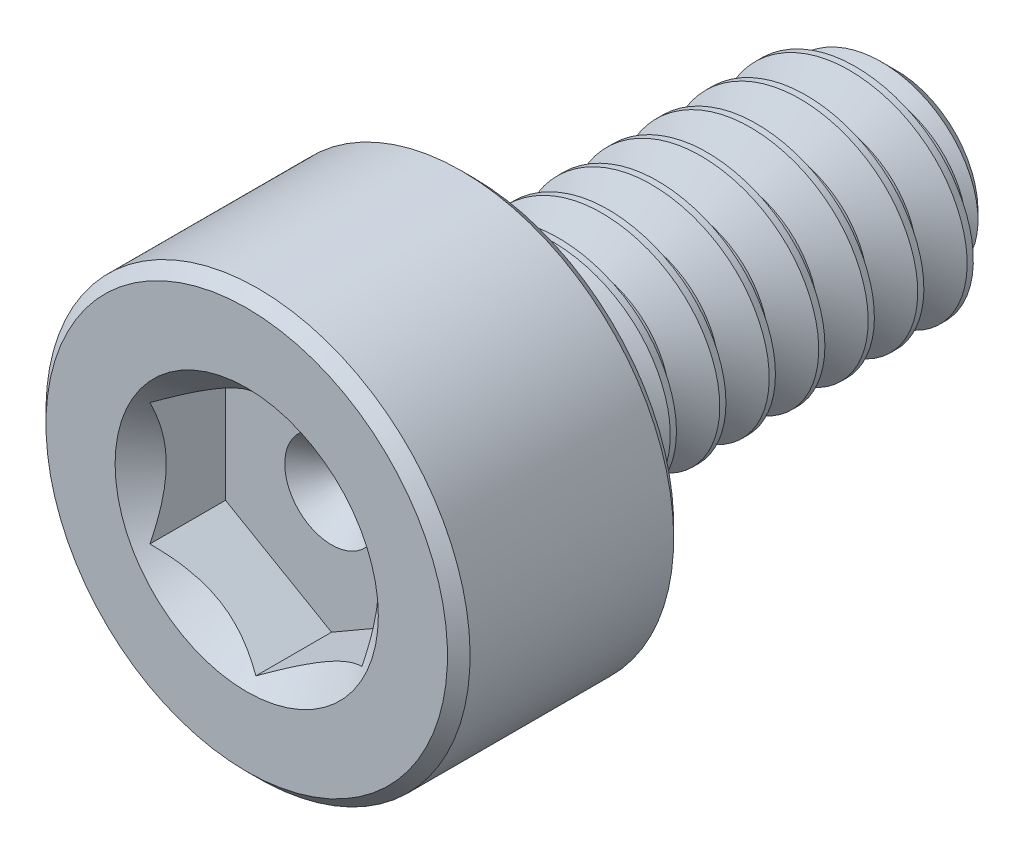
SolidWorks part; units mm, degrees
ref_plane "Front Plane" through (0, 0, 0) normal (0, 0, 1) x (1, 0, 0)
ref_plane "Top Plane" through (0, 0, 0) normal (0, 1, 0) x (1, 0, 0)
ref_plane "Right Plane" through (0, 0, 0) normal (1, 0, 0) x (0, 0, -1)
sketch "Sketch1" plane through (0, 0, 0) normal (1, 0, 0) x (0, 0, -1)
  line L0 (-2.3, 0) -> (2.3, 0) construction
  line L1 (2.3, 0) -> (2.3, 0.5727) construction
  line L2 (2.3, 0.5727) -> (2.0727, 0.8) construction
  line L3 (2.0727, 0.8) -> (2.0375, 0.8) construction
  line L4 (2.0375, 0.8) -> (-0.7, 0.8) construction
  line L5 (-0.7, 0.8) -> (-0.7, 1.5) construction
  line L6 (-0.7, 1.5) -> (-2.3, 1.5) construction
  line L7 (-2.3, 1.5) -> (-2.3, 0) construction
  line L8 (2.3, 0.5727) -> (2.3, 0.8) construction
  line L9 (2.2781, 0.8379) -> (2.4531, 0.5348) construction
  line L10 (2.4531, 0.5348) -> (2.6281, 0.8379) construction
  line L11 (2.6281, 0.8379) -> (2.2781, 0.8379) construction
  line L12 (2.4531, 0.8379) -> (2.4531, 0.8) construction
  line L13 (2.4531, 0.5348) -> (2.4531, 0.5727) construction
  line L14 (2.4312, 0.5727) -> (2.475, 0.5727) construction
  line L15 (2.3, 0.8) -> (2.6062, 0.8) construction
  line L16 (2.2891, 0.8189) -> (2.6172, 0.8189) construction
  line L17 (2.3, 0) -> (2.3, -0.8) construction
  line L18 (-0.78, 1.5) -> (-0.7, 1.42) construction
  line L19 (-2.22, 1.5) -> (-2.3, 1.42) construction
  line L20 (-0.7, 0.8) -> (-0.7, 0) construction
  line L21 (-0.7, 0.4) -> (0.3, 0.4) construction
  line L22 (0.3, 0.4) -> (1.3, 0.4) construction
  line L23 (1.3, 0.4) -> (2.3, 0.4) construction
  line L24 (0.3, 0.4) -> (0.3, 0.8) construction
  line L25 (0.3, 0.8) -> (0.3, 1.5) construction
  line L26 (1.3, 0.4) -> (1.3, 1.5) construction
  point P0 (-2.3, 0.75)
  point P3 (1.425, 0.8)
  point P4 (0, 0)
  point P18 (1.3, 0.8)
  point P22 (2.4531, 0.5727)
  point P24 (2.0375, 0.8)
  point P25 (2.4531, 0.8)
  point P28 (2.4531, 0.8189)
  point P29 (1.425, -0.8)
  point P30 (0.3, 0.8)
  point P31 (-1.5, 1.5)
  point P37 (-0.98, 1.5)
  point P38 (-2.18, 1.5)
  point P45 (0.3, 0.4)
  point P46 (1.3, 0.4)
  dimension "D2" = 0.0437
  dimension "D7" = 0.08
  dimension "D8" = 0.08
  dimension "D9" = 0.08
  dimension "D10" = 0.04
  dimension "D11" = 0.2
  dimension "Drive Size" = 1.5
  dimension "Head Diameter" = 3
  dimension "Head Height" = 1.6
  dimension "Thread Pitch" = 0.35
  dimension "Thread Dia" = 1.6
  dimension "Length" = 3
  dimension "D12" = 0.2625
  dimension "D4" = 0.875
  dimension "D3" = 45
sketch "Sketch2" plane through (0, 0, 0) normal (1, 0, 0) x (0, 0, -1)
  line L0 (-2.3, 0) -> (-2.3, 1.42)
  line L1 (-2.22, 1.5) -> (-0.78, 1.5)
  line L2 (-0.7, 1.42) -> (-0.7, 0.88)
  line L4 (2.0727, 0.8) -> (2.3, 0.5727)
  line L5 (2.3, 0.5727) -> (2.3, 0)
  line L6 (-0.7, 1.5) -> (-2.3, 1.5) construction
  line L7 (2.3, 0) -> (-2.3, 0)
  line L8 (-2.22, 1.5) -> (-2.3, 1.42) construction
  line L10 (-2.22, 1.5) -> (-2.3, 1.42)
  line L14 (-0.78, 1.5) -> (-0.7, 1.42) construction
  line L16 (-0.78, 1.5) -> (-0.7, 1.42)
  line L17 (-0.7, 0.8) -> (-0.7, 1.5) construction
  line L19 (-0.62, 0.8) -> (2.0727, 0.8)
  line L20 (2.0375, 0.8) -> (-0.7, 0.8) construction
  arc A1 (-0.7, 0.88) -> (-0.62, 0.8) centre (-0.62, 0.88) ccw
  dimension "D3" = 0.08
revolve "Revolve1" add sketch "Sketch2" angle 360 about L7
sketch "Sketch3" plane through (0, 0, 2.3) normal (0, 0, 1) x (1, 0, 0)
  line L1 (0.75, -0.433) -> (0.75, 0.433)
  line L2 (0.75, 0.433) -> (0, 0.866)
  line L3 (0, 0.866) -> (-0.75, 0.433)
  line L4 (-0.75, 0.433) -> (-0.75, -0.433)
  line L5 (-0.75, -0.433) -> (0, -0.866)
  line L6 (0, -0.866) -> (0.75, -0.433)
  circle A0 centre (0, 0) radius 0.75 construction
  circle A1 centre (0, 0) radius 1.5 construction
  circle A2 centre (0, 0) radius 1.5 construction
  circle A3 centre (0, 0) radius 0.866 construction
  point P13 (0, 0)
  dimension "D1" = 1.7321
extrude "Cut-Extrude1" cut sketch "Sketch3" against normal offset from surface (0.6 mm away) 1 up to face at (0, 1.42, 0.7)
sketch "Sketch4" plane through (0, 0, 2.3) normal (0, 0, 1) x (1, 0, 0)
  circle A0 centre (0, 0) radius 0.931
  dimension "D1" = 1.862
extrude "Cut-Extrude2" cut sketch "Sketch4" against normal up to vertex (0.8 mm away) draft 45 up to point (0, 1.5, 1.5)
sketch "Sketch11" plane through (0, 0, 0) normal (1, 0, 0) x (0, 0, -1)
  line L0 (-2.3, 0) -> (2.3, 0) construction
  line L1 (-2.3, 0) -> (2.3, 0) construction
  line L2 (-0.1375, 0) -> (-0.1375, 0.8) construction
  line L3 (2.0375, 0.8) -> (-0.7, 0.8) construction
  line L4 (1.7375, 0) -> (1.7375, 0.8) construction
  line L6 (2.3, 0.5727) -> (2.3, 0.8) construction
  point P2 (-0.1375, 0)
  point P3 (1.7375, 0)
  dimension "D1" = 0.5625
  dimension "D2" = 0.5625
sketch "Sketch6" plane through (0, 0, -2.3) normal (0, 0, -1) x (-1, 0, 0)
  circle A0 centre (0, 0) radius 0.8
curve "Helix/Spiral1" pitch 0.35 height 3.35 turns 9.5714
sketch "Sketch10" plane through (0, 0, 0) normal (1, 0, 0) x (0, 0, -1)
  line L0 (-0.62, -1.5) -> (-0.62, 1.5)
  line L5 (-2.3, 0) -> (2.3, 0) construction
  line L6 (-0.62, 0.8) -> (-0.62, -0.8) construction
  point P3 (-0.62, 0)
split "Split1" trim tools "Sketch10" bodies to split 106 resulting bodies 114 115
sketch "Sketch7" plane through (0, 0, 0) normal (1, 0, 0) x (0, 0, -1)
  line L0 (2.2891, 0.8189) -> (2.6172, 0.8189)
  line L1 (2.6172, 0.8189) -> (2.475, 0.5727)
  line L2 (2.475, 0.5727) -> (2.4312, 0.5727)
  line L3 (2.4312, 0.5727) -> (2.2891, 0.8189)
sweep "Cut-Sweep1" cut profiles "Sketch7" path "Helix/Spiral1" align with end faces yes
sketch "Sketch8" plane through (0, 0, 0) normal (1, 0, 0) x (0, 0, -1)
  line L0 (-0.7, 0) -> (-0.7, 0.8)
  line L1 (-0.62, -0.8) -> (-0.62, 0.8) construction
  line L2 (-0.7, 0.8) -> (-0.62, 0.8)
  line L4 (-0.62, 0.8) -> (-0.1581, 0)
  line L5 (-0.1581, 0) -> (-0.7, 0)
  line L6 (2.0375, 0.8) -> (-0.7, 0.8) construction
  line L7 (-2.3, 0) -> (2.3, 0) construction
  dimension "D1" = 60
revolve "Revolve2" add sketch "Sketch8" angle 360 about L5
equation "\"D2@Sketch1\" = \"Thread Pitch@Sketch1\" / 8"
equation "\"D4@Helix/Spiral1\" = \"Thread Pitch@Sketch1\""
equation "\"D7@Sketch1\" = \"Head Height@Sketch1\" * .05"
equation "\"D8@Sketch1\"=\"D7@Sketch1\""
equation "\"D9@Sketch1\"=\"D7@Sketch1\""
equation "\"D10@Sketch1\"=\"D7@Sketch1\"/2"
equation "\"D11@Sketch1\"=\"D10@Sketch1\"*5"
equation "\"D4@Sketch1\"=\"Thread Pitch@Sketch1\"*2.5"
equation "\"D12@Sketch1\"=\"Thread Pitch@Sketch1\"*.75"
equation "\"D3@Helix/Spiral1\"=\"Length@Sketch1\"+\"Thread Pitch@Sketch1\""
equation "\"D3@Sketch2\"=\"Thread Dia@Sketch1\"*0.05"
equation "\"D1@Sketch11\"=\"Length@Sketch1\"*0.1875"
equation "\"D2@Sketch11\"=\"D1@Sketch11\""
equation "\"D1@Sketch4\"=\"D1@Sketch3\"*1.075"
